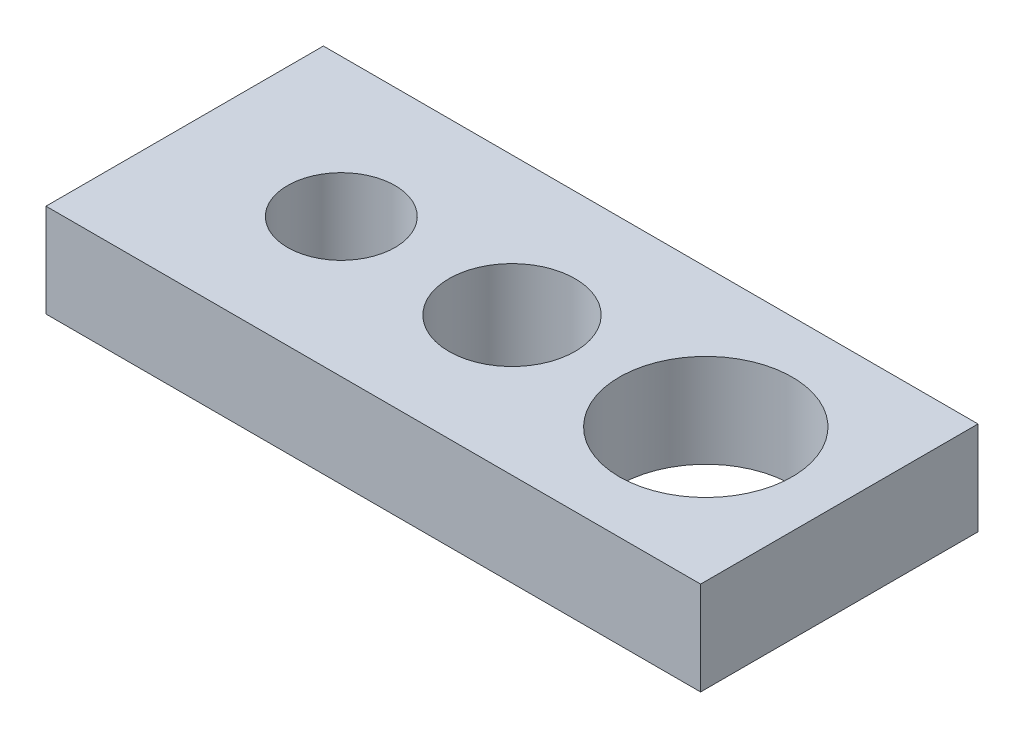
SolidWorks part; units mm, degrees
ref_plane "Front Plane" through (0, 0, 0) normal (0, 0, 1) x (1, 0, 0)
ref_plane "Top Plane" through (0, 0, 0) normal (0, 1, 0) x (1, 0, 0)
ref_plane "Right Plane" through (0, 0, 0) normal (1, 0, 0) x (0, 0, -1)
ref_axis "X" through (-88.99, 0, 0) along (1, 0, 0)
ref_axis "Y" through (0, 55, 0) along (0, -1, 0)
ref_axis "Z" through (0, 0, -88.99) along (0, 0, 1)
sketch "Sketch1" plane through (0, 0, 0) normal (0, 1, 0) x (1, 0, 0)
  line L1 (-7.0057, 2.9688) -> (7.0057, 2.9688)
  line L2 (-7.0057, 2.9688) -> (-7.0057, -2.9688)
  line L3 (-7.0057, -2.9688) -> (7.0057, -2.9688)
  line L4 (7.0057, 2.9688) -> (7.0057, -2.9688)
  line L5 (-7.0057, 2.9688) -> (7.0057, -2.9688) construction
  line L6 (-7.0057, -2.9688) -> (7.0057, 2.9688) construction
  circle A0 centre (-3.6538, 0) radius 1.15
  circle A1 centre (0, 0) radius 1.35
  circle A2 centre (4.1479, 0) radius 1.85
  point P0 (0, 0)
  point P12 (-7.8683, -3.4624)
  point P13 (3.7915, -0.2816)
  point P14 (0, 0)
  point P15 (-3.6538, 0)
  point P16 (4.1479, 0)
  point P17 (-7.0057, -2.9688)
  dimension "D1" = 2.3
  dimension "D2" = 2.7
  dimension "D3" = 3.7
extrude "Boss-Extrude1" add sketch "Sketch1" along normal blind 2
